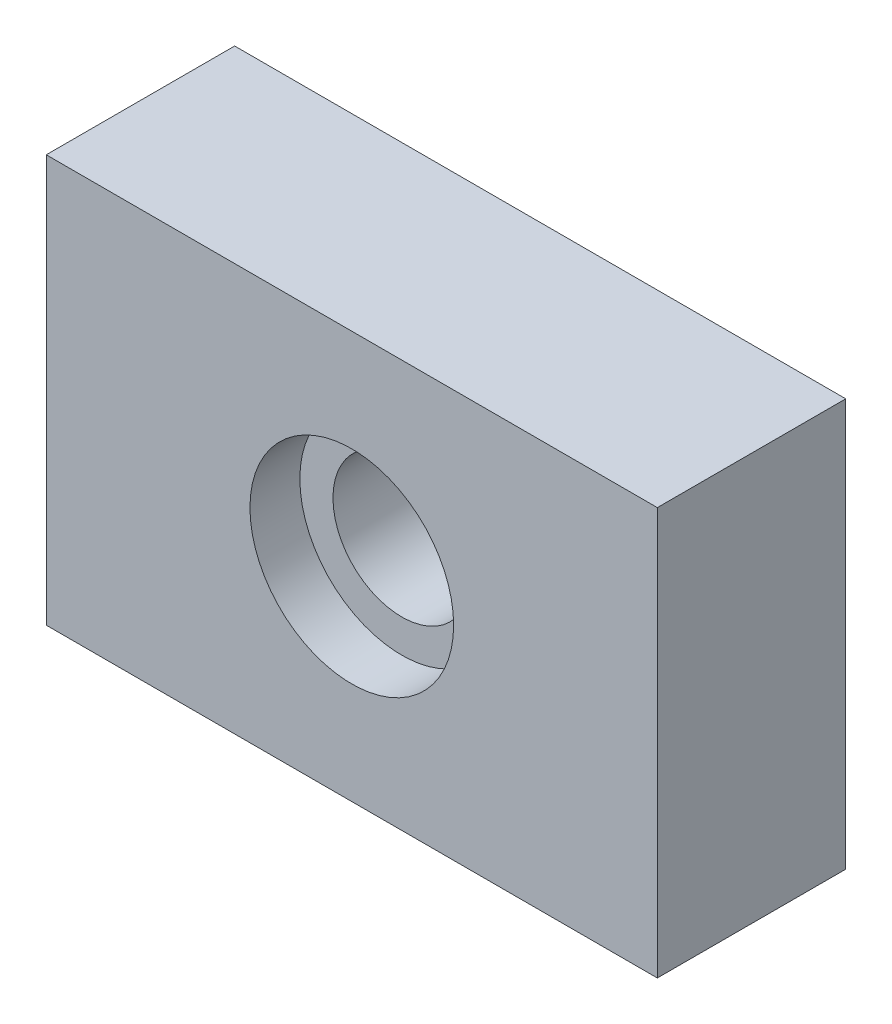
SolidWorks part; units mm, degrees
material "1060 Alloy"
ref_plane "Front Plane" through (0, 0, 0) normal (0, 0, 1) x (1, 0, 0)
ref_plane "Top Plane" through (0, 0, 0) normal (0, 1, 0) x (1, 0, 0)
ref_plane "Right Plane" through (0, 0, 0) normal (1, 0, 0) x (0, 0, -1)
sketch "Sketch1" plane through (0, 0, 0) normal (0, 0, 1) x (1, 0, 0)
  line L1 (0, 0) -> (152.4, 0)
  line L2 (0, 0) -> (0, 101.6)
  line L3 (0, 101.6) -> (152.4, 101.6)
  line L4 (152.4, 0) -> (152.4, 101.6)
  dimension "D1" = 152.4
  dimension "D2" = 101.6
extrude "Boss-Extrude1" add sketch "Sketch1" along normal blind 46.99
sketch "Sketch2" plane through (0, 0, 0) normal (0, 0, -1) x (-1, 0, 0)
  line L0 (0, 50.8) -> (-152.4, 50.8) construction
  line L1 (0, 101.6) -> (0, 0) construction
  line L2 (-152.4, 0) -> (-152.4, 101.6) construction
  line L4 (-152.4, 101.6) -> (0, 101.6) construction
  line L5 (-76.2, 101.6) -> (-76.2, 0) construction
  line L6 (0, 0) -> (-152.4, 0) construction
  circle A0 centre (-76.2, 50.8) radius 25.4
  circle A1 centre (-76.2, 50.8) radius 17.145
  dimension "D1" = 50.8
  dimension "D2" = 34.29
extrude "Cut-Extrude1" cut sketch "Sketch2" against normal through all contours A1
extrude "Cut-Extrude3" cut sketch "Sketch2<2>" against normal blind 12.446
sketch "Sketch2<2>" plane through (0, 0, 0) normal (0, 0, -1) x (-1, 0, 0) same geometry as "Sketch2"
ref_plane "Plane2" through (0, 0, 23.495) normal (0, 0, -1) x (-1, 0, 0)
mirror "Mirror2" about plane through (0, 0, 23.495) normal (0, 0, -1) of "Cut-Extrude3"
hole_wizard "Tap Drill for 1/2-13 Tap1" positions "Sketch4" profile "Sketch5" hole size "1/2-13" standard "ANSI Inch"
sketch "Sketch4" plane through (0, 0, 0) normal (0, -1, 0) x (-1, 0, 0)
  line L0 (55.88, -23.495) -> (-55.88, -23.495) construction
  line L2 (-76.2, -46.99) -> (-76.2, 0) construction
  line L3 (0, -46.99) -> (-152.4, -46.99) construction
  line L4 (0, 0) -> (-152.4, 0) construction
  point P0 (-68.0517, -23.495)
  point P4 (-29.9517, -23.495)
  dimension "D1" = 46.2483
  dimension "D2" = 38.1
sketch "Sketch5" plane through (68.0517, 0, 23.495) normal (1, 0, 0) x (0, 0, -1)
  line L0 (0, 0) -> (0, 22.2695)
  line L1 (0, 22.2695) -> (5.3581, 19.05)
  line L2 (5.3581, 19.05) -> (5.3581, 0)
  line L5 (5.3581, 0) -> (0, 0)
  line L10 (0, 22.2695) -> (-5.3581, 19.05) construction
  line L11 (0, -6.35) -> (0, 107.95) construction
  dimension "Hole Dia." = 10.7163
  dimension "Hole Depth" = 19.05
  dimension "Drill Angle" = 118
equation "\"through_diamiter\"= 1.35"
equation "\"D2@Sketch2\"= \"through_diamiter\""
equation "\"bearing depth\"= 0.5"
equation "\"hole spacing\"= 0.75"
equation "\"D1@Sketch4\" = \"hole spacing\"+\"center_distance\""
equation "\"center_distance\" = 1.07080043"
